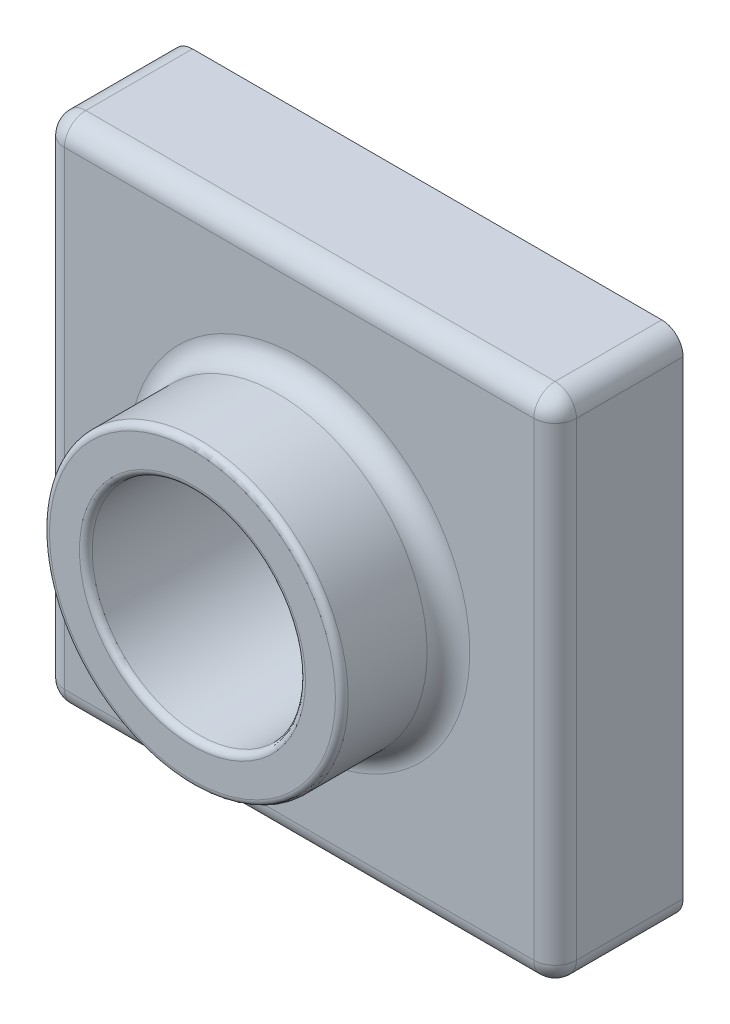
SolidWorks part; units mm, degrees
material "Acier inoxydable chromé"
ref_plane "Plan de face" through (0, 0, 0) normal (0, 0, 1) x (1, 0, 0)
ref_plane "Plan de dessus" through (0, 0, 0) normal (0, 1, 0) x (1, 0, 0)
ref_plane "Plan de droite" through (0, 0, 0) normal (1, 0, 0) x (0, 0, -1)
sketch "Esquisse2" plane through (0, 0, 0) normal (0, 0, 1) x (1, 0, 0)
  line L1 (0, 0) -> (120, 0)
  line L2 (0, 0) -> (0, 120)
  line L3 (0, 120) -> (120, 120)
  line L4 (120, 0) -> (120, 120)
  dimension "D1" = 120
  dimension "D2" = 120
extrude "Boss.-Extru.1" add sketch "Esquisse2" along normal blind 30
sketch "Esquisse3" plane through (0, 0, 30) normal (0, 0, 1) x (1, 0, 0)
  line L0 (0, 0) -> (120, 0) construction
  line L1 (0, 120) -> (0, 0) construction
  circle A0 centre (60, 60) radius 35
  point P0 (60, 60)
  dimension "D3" = 70
  dimension "D1" = 60
  dimension "D2" = 60
extrude "Boss.-Extru.3" add sketch "Esquisse3" along normal blind 25
sketch "Esquisse9" plane through (0, 0, 55) normal (0, 0, 1) x (1, 0, 0)
  circle A2 centre (60, 60) radius 25
  circle A3 centre (60, 60) radius 25
  dimension "D2" = 50
  dimension "D1" = 10
extrude "Enlèv. mat.-Extru.1" cut sketch "Esquisse9" against normal through all
fillet "Congé1" radius 5 9 edges at (0, 0, 15) (0, 120, 15) (0, 60, 30) (60, 0, 30) (120, 0, 15) (120, 60, 30) (60, 120, 30) (120, 120, 15) (95, 60, 30)
fillet "Congé2" radius 1.5 2 edges at (85, 60, 55) (95, 60, 55)
shell "Coque1" thickness 2 removed face at (85, 60, 0)
